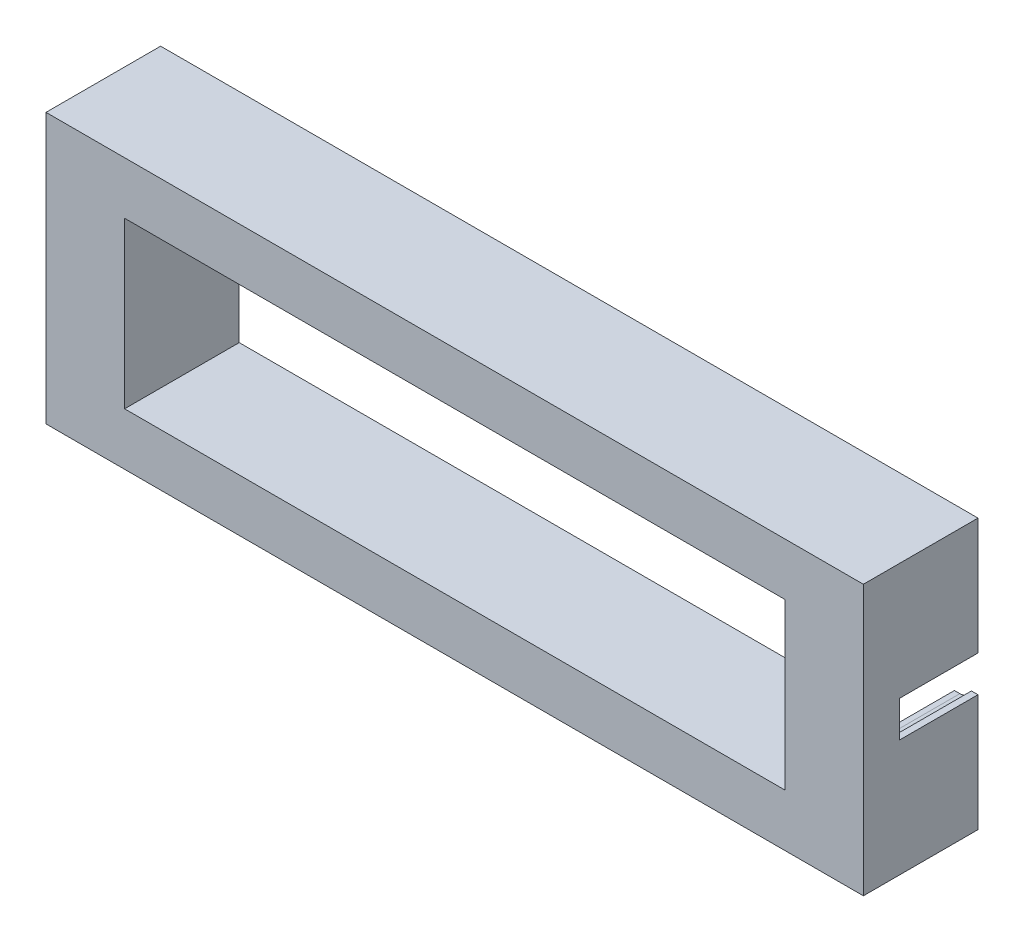
SolidWorks part; units mm, degrees
material "STEEL"
ref_plane "Front Plane" through (0, 0, 0) normal (0, 0, 1) x (1, 0, 0)
ref_plane "Top Plane" through (0, 0, 0) normal (0, 1, 0) x (1, 0, 0)
ref_plane "Right Plane" through (0, 0, 0) normal (1, 0, 0) x (0, 0, -1)
sketch "Sketch1" plane through (0, 0, 0) normal (0, 0, 1) x (1, 0, 0)
  line L1 (-79.24, -26.16) -> (79.24, -26.16)
  line L2 (-79.24, -26.16) -> (-79.24, 26.16)
  line L3 (-79.24, 26.16) -> (79.24, 26.16)
  line L4 (79.24, -26.16) -> (79.24, 26.16)
  line L5 (0, 26.16) -> (0, -26.16) construction
  line L6 (-79.24, 0) -> (79.24, 0) construction
  line L7 (64, -16) -> (-64, -16) construction
  line L8 (64, -16) -> (64, 16) construction
  line L9 (64, 16) -> (-64, 16) construction
  line L10 (-64, -16) -> (-64, 16) construction
  line L11 (0, 16) -> (0, -16) construction
  line L12 (64, 0) -> (-64, 0) construction
  point P0 (0, 0)
  point P4 (0, 0)
  dimension "D1" = 15.24
  dimension "D2" = 15.24
  dimension "D3" = 32
  dimension "D4" = 128
  dimension "D5" = 10.16
extrude "Boss-Extrude1" add sketch "Sketch1" along normal blind 22.225
sketch "Sketch2" plane through (0, 0, 0) normal (0, 0, -1) x (-1, 0, 0)
  line L1 (-64, -16) -> (64, -16)
  line L2 (-64, -16) -> (-64, 16)
  line L3 (-64, 16) -> (64, 16)
  line L4 (64, -16) -> (64, 16)
extrude "Cut-Extrude1" cut sketch "Sketch2" against normal through all
sketch "Sketch4" plane through (0, 0, 0) normal (0, 0, -1) x (-1, 0, 0)
  line L0 (-74.668, 5.08) -> (-77.97, 5.08)
  line L1 (-64, -16) -> (-64, 16) construction
  line L2 (-77.97, 5.08) -> (-77.97, 3.5)
  line L3 (-77.97, 3.5) -> (-79.24, 3.5)
  line L4 (-79.24, -26.16) -> (-79.24, 26.16) construction
  line L5 (-79.24, 3.5) -> (-79.24, 0)
  line L6 (-79.24, 0) -> (-64, 0)
  line L7 (-64, 0) -> (-64, 5.08)
  line L9 (-64, 16) -> (-74.668, 16)
  line L10 (-64, 16) -> (-64, 5.08)
  line L12 (-74.668, 16) -> (-74.668, 5.08)
  point P8 (-77.97, 4.29)
  dimension "D1" = 3.5
  dimension "D2" = 13.97
  dimension "D3" = 5.08
  dimension "D4" = 10.668
extrude "Cut-Extrude2" cut sketch "Sketch4" against normal blind 15.24
mirror "Mirror1" about plane through (0, 0, 0) normal (0, 1, 0) of "Cut-Extrude2"
fillet "Fillet1" radius 2.3813 4 edges at (74.668, -16, 7.62) (77.97, -5.08, 7.62) (74.668, 16, 7.62) (77.97, 5.08, 7.62)
